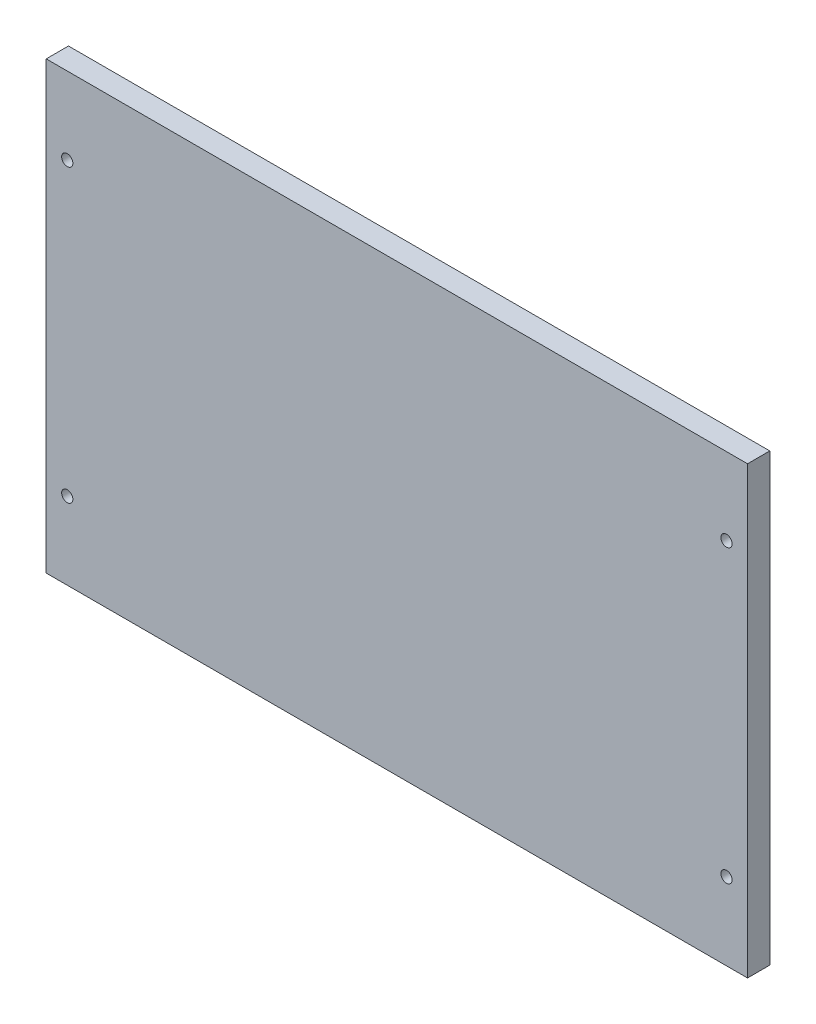
SolidWorks part; units mm, degrees
ref_plane "Front Plane" through (0, 0, 0) normal (0, 0, 1) x (1, 0, 0)
ref_plane "Top Plane" through (0, 0, 0) normal (0, 1, 0) x (1, 0, 0)
ref_plane "Right Plane" through (0, 0, 0) normal (1, 0, 0) x (0, 0, -1)
sketch "Sketch1" plane through (0, 0, 0) normal (0, 0, 1) x (1, 0, 0)
  line L0 (100, 127) -> (100, 0) construction
  line L1 (0, 0) -> (200, 0)
  line L2 (0, 0) -> (0, 127)
  line L3 (0, 127) -> (200, 127)
  line L4 (200, 0) -> (200, 127)
  line L5 (0, 63.5) -> (200, 63.5) construction
  circle A3 centre (6, 105) radius 1.6
  circle A7 centre (194, 105) radius 1.6
  circle A8 centre (194, 22) radius 1.6
  circle A9 centre (6, 22) radius 1.6
  dimension "D11" = 3.2
  dimension "D1" = 127
  dimension "D2" = 200
  dimension "D12" = 6
  dimension "D13" = 22
extrude "Wall" add sketch "Sketch1" along normal blind 6.35
sketch "Sketch2" [suppressed] plane through (0, 0, 6.35) normal (0, 0, 1) x (1, 0, 0)
  line L0 (135.35, 127) -> (135.35, 98.425) construction
  line L1 (270.7, 127) -> (0, 127) construction
  line L2 (135.35, 98.425) -> (66.6667, 98.425) construction
  line L3 (135.35, 98.425) -> (204.0333, 98.425) construction
  line L4 (0, 127) -> (0, 0) construction
  circle A0 centre (135.35, 98.425) radius 3.9687
  circle A1 centre (66.6667, 98.425) radius 3.9688
  circle A2 centre (204.0333, 98.425) radius 3.9687
  dimension "D2" = 7.9375
  dimension "D1" = 28.575
  dimension "D3" = 66.6667
extrude "RodSupportCutouts" [suppressed] cut sketch "Sketch2" against normal up to next
sketch "Sketch3" [suppressed] plane through (0, 0, 6.35) normal (0, 0, 1) x (1, 0, 0)
  line L1 (25.4, 88.9) -> (245.3, 88.9)
  line L2 (25.4, 88.9) -> (25.4, 114.3)
  line L3 (25.4, 114.3) -> (245.3, 114.3)
  line L4 (245.3, 88.9) -> (245.3, 114.3)
  line L5 (25.4, 88.9) -> (245.3, 114.3) construction
  line L6 (25.4, 114.3) -> (245.3, 88.9) construction
  line L7 (270.7, 127) -> (0, 127) construction
  line L8 (0, 127) -> (0, 0) construction
  point P0 (135.35, 101.6)
  point P9 (135.35, 127)
  dimension "D1" = 25.4
  dimension "D2" = 25.4
  dimension "D3" = 25.4
extrude "CannulaLargeCutout" [suppressed] cut sketch "Sketch3" against normal up to next
sketch "Sketch4" [suppressed] plane through (0, 0, 9.525) normal (0, 0, 1) x (1, 0, 0)
  line L0 (6, 103.5) -> (194, 103.5) construction
  line L1 (6, 105) -> (6, 22) construction
  line L2 (194, 105) -> (194, 22) construction
  line L3 (200, 127) -> (0, 127) construction
  line L4 (0, 127) -> (0, 0) construction
  circle A0 centre (60, 103.5) radius 6.35
  circle A1 centre (20, 103.5) radius 6.35
  circle A2 centre (100, 103.5) radius 6.35
  circle A3 centre (140, 103.5) radius 6.35
  circle A4 centre (60, 63.5) radius 6.35
  circle A5 centre (100, 63.5) radius 6.35
  circle A6 centre (140, 63.5) radius 6.35
  circle A7 centre (60, 23.5) radius 6.35
  circle A8 centre (100, 23.5) radius 6.35
  circle A9 centre (140, 23.5) radius 6.35
  circle A10 centre (20, 63.5) radius 6.35
  circle A11 centre (20, 23.5) radius 6.35
  circle A12 centre (180, 103.5) radius 6.35
  circle A13 centre (180, 63.5) radius 6.35
  circle A14 centre (180, 23.5) radius 6.35
  point P42 (100, 127)
  point P45 (0, 63.5)
  dimension "D3" = 12.7
  dimension "D1" = 5
  dimension "D2" = 3
extrude "CannulaHoles" [suppressed] cut sketch "Sketch4" against normal up to next
ref_plane "LeftBoundary" [suppressed] through (25.4, 0, 0) normal (-1, 0, 0) x (0, 0, 1)
ref_plane "RightBoundary" [suppressed] through (245.3, 0, 0) normal (1, 0, 0) x (0, 0, -1)
ref_plane "TopBoundary" [suppressed] through (0, 101.6, 0) normal (0, 1, 0) x (1, 0, 0)
ref_plane "BottomBoundary" [suppressed] through (0, 25.4, 0) normal (0, -1, 0) x (-1, 0, 0)
sketch "Sketch5" [suppressed] plane through (0, 0, 6.35) normal (0, 0, 1) x (1, 0, 0)
  line L4 (25.4, 3.4925) -> (25.4, -3.4925) construction
  line L5 (3.4925, 101.6) -> (-3.4925, 101.6) construction
  circle A0 centre (25.4, 101.6) radius 3.9687
  dimension "D1" = 7.9375
extrude "RodSupportCutout" [suppressed] cut sketch "Sketch5" along normal blind 3.35 from surface starting at face at (4.4, 22, 0)
pattern_linear "SupportPattern" [suppressed] count 7 spacing 36.65 count 5 spacing 19.05 of bodies 105
sketch "Sketch6" [suppressed] plane through (0, 0, 6.35) normal (0, 0, 1) x (1, 0, 0)
  line L0 (47, 107.95) -> (50.5, 107.95)
  line L1 (149.5, 107.95) -> (153, 107.95)
  line L2 (149.5, 107.95) -> (149.5, 31.75)
  line L3 (149.5, 31.75) -> (153, 31.75)
  line L4 (153, 107.95) -> (153, 31.75)
  line L5 (47, 107.95) -> (47, 31.75)
  line L6 (47, 31.75) -> (50.5, 31.75)
  line L7 (50.5, 107.95) -> (50.5, 31.75)
  line L8 (0, 127) -> (0, 0) construction
  line L9 (0, 0) -> (200, 0) construction
  line L10 (200, 0) -> (200, 127) construction
  line L11 (0, 0) -> (200, 0) construction
  point P7 (200, 57)
  dimension "D1" = 76.2
  dimension "D2" = 31.75
  dimension "D3" = 3.5
  dimension "SlitDiameter" = 3.5
  dimension "D4" = 47
  dimension "D5" = 47
  dimension "D6" = 31.75
  dimension "D7" = 76.2
extrude "Cut-Extrude1" [suppressed] cut sketch "Sketch6" against normal through all
equation "\"Length\"= 283mm"
equation "\"Width\"= 225mm"
equation "\"WallThickness\"= 0.25in"
equation "\"UpperWaterJacketThickness\"= 28mm"
equation "\"SpacerHeight\"= 80.2mm"
equation "\"SpacerCornerWidth\"= 10mm"
equation "\"SpacerCornerHeight\"= 60.16mm"
equation "\"SpacerPegDiameter\"= 10mm"
equation "\"SpacerPegHeight\"= 10mm"
equation "\"TubingShort\"= 110mm"
equation "\"TubingLong\"= 175mm"
equation "\"PlateLength\"= 252mm"
equation "\"PlateWidth\"= 190mm"
equation "\"PlateHoleDiameter\"= 5.9mm"
equation "\"PlateHoleBottom\"= 2mm"
equation "\"PlateHoleSide\"= 1.55mm"
equation "\"PlateHoleSpacing\"= 3.1mm"
equation "\"PlateThickness\"= 1.55mm"
equation "\"ReservoirBottom\"= 12.5mm"
equation "\"ReservoirSupportWidth\"= 12mm"
equation "\"ReservoirSupportHeight\"= 15.1mm"
equation "\"ReservoirSupportPlacementHeight\"= 50mm"
equation "\"ReservoirHoleDiameter\"= 12.7mm"
equation "\"ReservoirHoleRight\"= 25mm"
equation "\"ReservoirHoleTop\"= \"ReservoirSupportPlacementHeight\""
equation "\"ReservoirHeight\"= 90mm"
equation "\"ReservoirPortBottom\"= 4mm"
equation "\"ReservoirPortTop\"= 10mm"
equation "\"ReservoirPortWidth\"= 101mm"
equation "\"CustomSpacerHeight\"= 5in"
equation "\"CustomSpacerRodHoleHeight\"= .75in"
equation "\"CustomSpacerRodHoleDiameter\"= .3125in"
equation "\"ScrewBlockSide\"= 12mm"
equation "\"ScrewBlockUpperHeight\"= 16mm"
equation "\"ScrewBlockLowerHeight\"= 16mm"
equation "\"InternalLength\"= 258mm"
equation "\"InternalWidth\"= 200mm"
equation "\"CustomSpacerPegHeight\"= 1in"
equation "\"CustomSpacerScrewBore\"=3.2mm"
equation "\"CustomSpacerScrewDepth\"=10mm"
equation "\"D1@Sketch1\"=\"CustomSpacerHeight\""
equation "\"D2@Sketch1\"=\"WallLength\""
equation "\"D11@Sketch1\"=\"CustomSpacerScrewBore\""
equation "\"D12@Sketch1\"   = \"ScrewBlockSide\"/2"
equation "\"D13@Sketch1\"=\"ScrewBlockUpperHeight\"+\"ScrewBlockSide\"/2"
equation "\"D1@Wall\" = \"WallThickness\""
equation "\"D1@Sketch2\"=\"CustomSpacerRodHoleHeight\" + \"CustomSpacerRodHoleDiameter\" +0.0625in"
equation "\"D2@Sketch2\"=\"CustomSpacerRodHoleDiameter\""
equation "\"D3@Sketch2\"=\"InternalWidth\" / 3"
equation "\"D1@Sketch3\"=1in"
equation "\"WallLength\"= \"InternalWidth\""
equation "\"D1@Sketch5\"=\"CustomSpacerRodHoleDiameter\""
equation "\"D1@RodSupportCutout\"      = \"WallThickness\" - 3"
